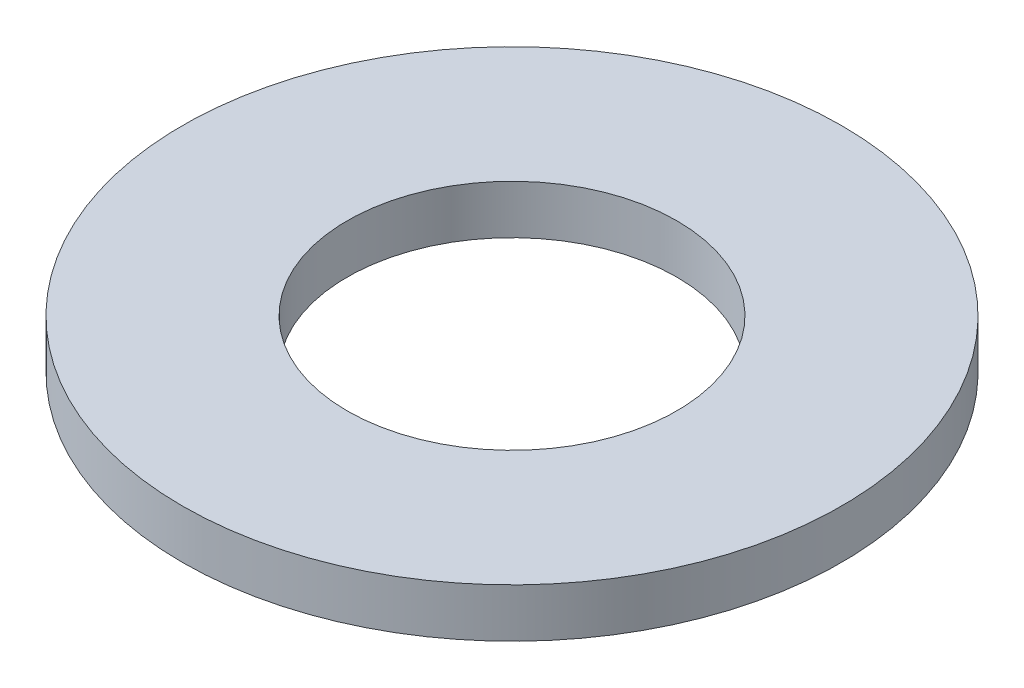
SolidWorks part; units mm, degrees
material "AISI 4130 Steel, normalized at 870C"
ref_plane "Front Plane" through (0, 0, 0) normal (0, 0, 1) x (1, 0, 0)
ref_plane "Top Plane" through (0, 0, 0) normal (0, 1, 0) x (1, 0, 0)
ref_plane "Right Plane" through (0, 0, 0) normal (1, 0, 0) x (0, 0, -1)
sketch "Sketch1" plane through (0, 0, 0) normal (0, 1, 0) x (1, 0, 0)
  circle A0 centre (0, 0) radius 4.3688
  circle A1 centre (0, 0) radius 8.7376
  dimension "ID" = 8.7376
  dimension "OD" = 17.4752
sketch "Sketch2" plane through (0, 0, 0) normal (1, 0, 0) x (0, 0, -1)
  line L1 (-8.7376, 0.6477) -> (8.7376, 0.6477)
  line L2 (-8.7376, 0.6477) -> (-8.7376, -0.6477)
  line L3 (-8.7376, -0.6477) -> (8.7376, -0.6477)
  line L4 (8.7376, 0.6477) -> (8.7376, -0.6477)
  line L5 (-8.7376, 0.6477) -> (8.7376, -0.6477) construction
  line L6 (-8.7376, -0.6477) -> (8.7376, 0.6477) construction
  point P0 (0, 0)
  point P6 (8.7376, 0)
  point P7 (-8.7376, 0)
  dimension "Thickness Range [Min]" = 1.2954
sketch "Sketch3" plane through (0, 0, 0) normal (0, 1, 0) x (1, 0, 0)
  circle A0 centre (0, 0) radius 8.7376
  circle A1 centre (0, 0) radius 4.3688
  circle A2 centre (0, 0) radius 8.7376 construction
  circle A3 centre (0, 0) radius 4.3688 construction
extrude "Boss-Extrude1" add sketch "Sketch3" along normal up to vertex (0.6477 mm away) and the other way up to vertex (0.6477 mm away) up to point (0, 0.6477, -8.7376) other way up to point (0, -0.6477, -8.7376)
move or copy body "Body-Move/Copy1" [suppressed] bodies to move or copy 101 parameters "D1"=0, "D2"=0, "D3"=0
move or copy body "Body-Move/Copy2" [suppressed] bodies to move or copy 104 parameters "D1"=0, "D2"=0, "D3"=0
